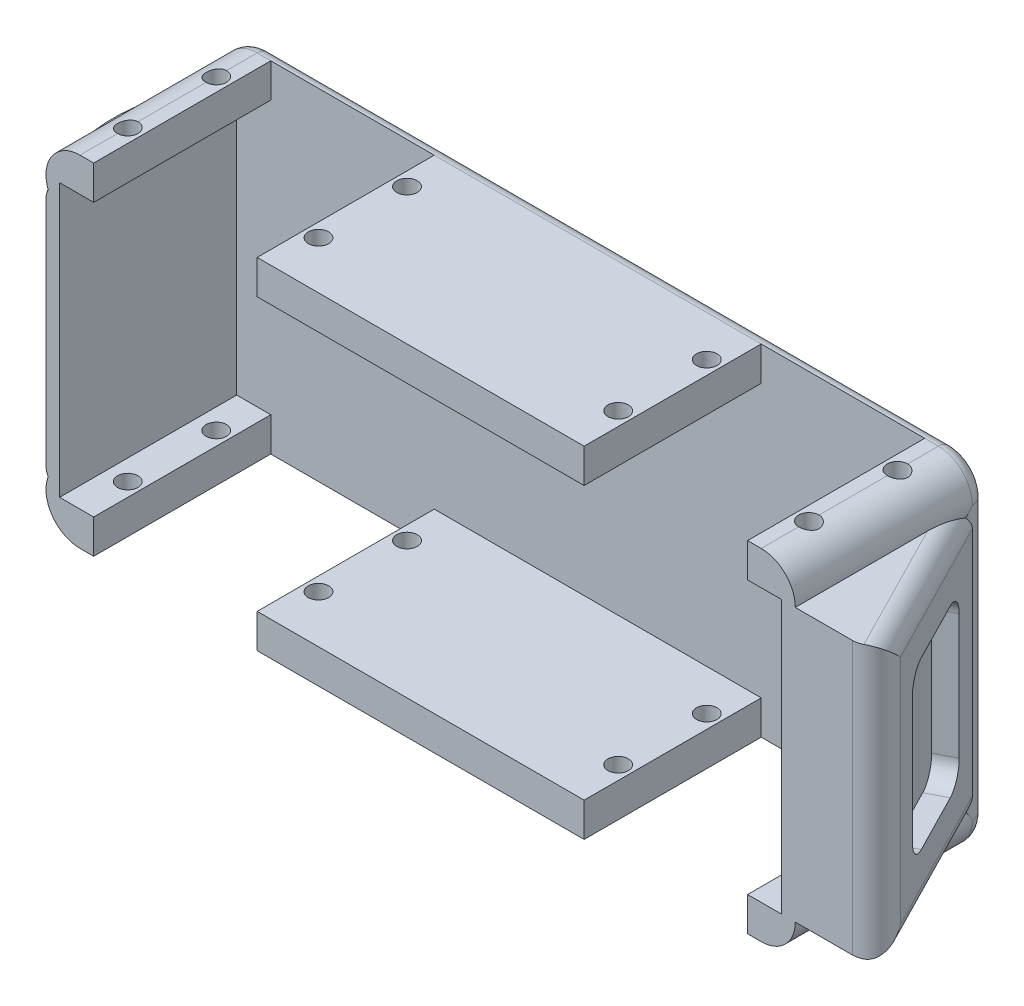
SolidWorks part; units mm, degrees
ref_plane "Front Plane" through (0, 0, 0) normal (0, 0, 1) x (1, 0, 0)
ref_plane "Top Plane" through (0, 0, 0) normal (0, 1, 0) x (1, 0, 0)
ref_plane "Right Plane" through (0, 0, 0) normal (1, 0, 0) x (0, 0, -1)
sketch "Sketch1" plane through (0, 0, 0) normal (0, 0, 1) x (1, 0, 0)
  line L1 (-55, 25) -> (55, 25)
  line L2 (-55, 25) -> (-55, -25)
  line L3 (-55, -25) -> (55, -25)
  line L4 (55, 25) -> (55, -25)
  line L5 (-55, 25) -> (55, -25) construction
  line L6 (-55, -25) -> (55, 25) construction
  point P0 (0, 0)
  dimension "D1" = 50
  dimension "D2" = 110
extrude "Boss-Extrude1" add sketch "Sketch1" along normal blind 28
sketch "Sketch2" plane through (0, 0, 28) normal (0, 0, 1) x (1, 0, 0)
  line L0 (-55, 25) -> (-55, -25) construction
  line L1 (-53, 20) -> (53, 20)
  line L2 (-53, 20) -> (-53, -20)
  line L3 (-53, -20) -> (53, -20)
  line L4 (53, 20) -> (53, -20)
  line L5 (-53, 20) -> (53, -20) construction
  line L6 (-53, -20) -> (53, 20) construction
  point P0 (0, 0)
  dimension "D1" = 40
  dimension "D2" = 2
extrude "Cut-Extrude1" cut sketch "Sketch2" against normal blind 26
fillet "Fillet1" radius 2 4 edges at (55, 0, 0) (0, -25, 0) (-55, 0, 0) (0, 25, 0)
fillet "Fillet2" radius 5 8 edges at (-54.4142, 24.4142, 0.5858) (-54.4142, -24.4142, 0.5858) (54.4142, 24.4142, 0.5858) (54.4142, -24.4142, 0.5858) (55, -25, 15) (55, 25, 15) (-55, -25, 15) (-55, 25, 15)
sketch "Sketch3" plane through (0, 0, 28) normal (0, 0, 1) x (1, 0, 0)
  line L0 (50, 25) -> (-50, 25) construction
  line L1 (-48, 20) -> (-24, 20)
  line L2 (-48, 20) -> (-48, 25)
  line L3 (-48, 25) -> (-24, 25)
  line L4 (-24, 20) -> (-24, 25)
  line L5 (53, 20) -> (-53, 20) construction
  line L10 (-55, 20) -> (-55, -20) construction
  point P7 (-32.0478, 20)
  dimension "D1" = 24
  dimension "D2" = 7
extrude "Cut-Extrude3" cut sketch "Sketch3" against normal blind 26
sketch "Sketch4" plane through (0, 25, 0) normal (0, 1, 0) x (1, 0, 0)
  line L0 (-50, -8) -> (-22, -8) construction
  line L1 (-36, -2) -> (-36, -8) construction
  line L2 (-24, -2) -> (-48, -2) construction
  circle A0 centre (-50, -8) radius 1.5
  circle A1 centre (-22, -8) radius 1.5
  dimension "D3" = 3
  dimension "D1" = 6
  dimension "D2" = 28
extrude "Cut-Extrude4" cut sketch "Sketch4" against normal blind 15
pattern_linear "LPattern1" count 2 spacing 13 along (0, 0, 1) of "Cut-Extrude4"
mirror "Mirror4" about plane through (0, 0, 0) normal (1, 0, 0) of "LPattern1", "Cut-Extrude3", "Cut-Extrude4" second plane through (0, 0, 0) second plane normal (0, 1, 0)
sketch "Sketch5" plane through (0, 0, 0) normal (0, 1, 0) x (1, 0, 0)
  line L0 (55, -2) -> (68.278, -28)
  line L1 (68.278, -28) -> (55, -28)
  line L2 (55, -28) -> (55, -2)
  line L3 (-55, -2) -> (-55, -28)
  arc A0 (-55, -2) -> (-55, -28) centre (-36.1015, -15) ccw
extrude "Boss-Extrude2" add sketch "Sketch5" along normal blind 20 and the other way blind 20
fillet "Fillet3" radius 3 2 edges at (-59.0395, 20, 15) (-59.0395, -20, 15)
fillet "Fillet4" radius 3 3 edges at (61.639, 20, 15) (68.278, 0, 28) (61.639, -20, 15)
sketch "Sketch6" plane through (42.8127, 0, -21.8642) normal (0.8906, 0, -0.4548) x (-0.4548, 0, -0.8906)
  line L0 (0, 0) -> (-39.1361, 0) construction
  line L1 (-44.0283, 12.1918) -> (-34.2438, 12.1918)
  line L2 (-47.0283, 9.1918) -> (-47.0283, -9.1918)
  line L3 (-44.0283, -12.1918) -> (-34.2438, -12.1918)
  line L4 (-31.2438, 9.1918) -> (-31.2438, -9.1918)
  line L5 (-47.0283, 12.1918) -> (-31.2438, -12.1918) construction
  line L6 (-47.0283, -12.1918) -> (-31.2438, 12.1918) construction
  arc A0 (-47.0283, -9.1918) -> (-44.0283, -12.1918) centre (-44.0283, -9.1918) ccw
  arc A1 (-34.2438, -12.1918) -> (-31.2438, -9.1918) centre (-34.2438, -9.1918) ccw
  arc A2 (-34.2438, 12.1918) -> (-31.2438, 9.1918) centre (-34.2438, 9.1918) cw
  arc A3 (-44.0283, 12.1918) -> (-47.0283, 9.1918) centre (-44.0283, 9.1918) ccw
  point P0 (-39.1361, 0)
  dimension "D1" = 3
extrude "Cut-Extrude5" cut sketch "Sketch6" against normal blind 3
